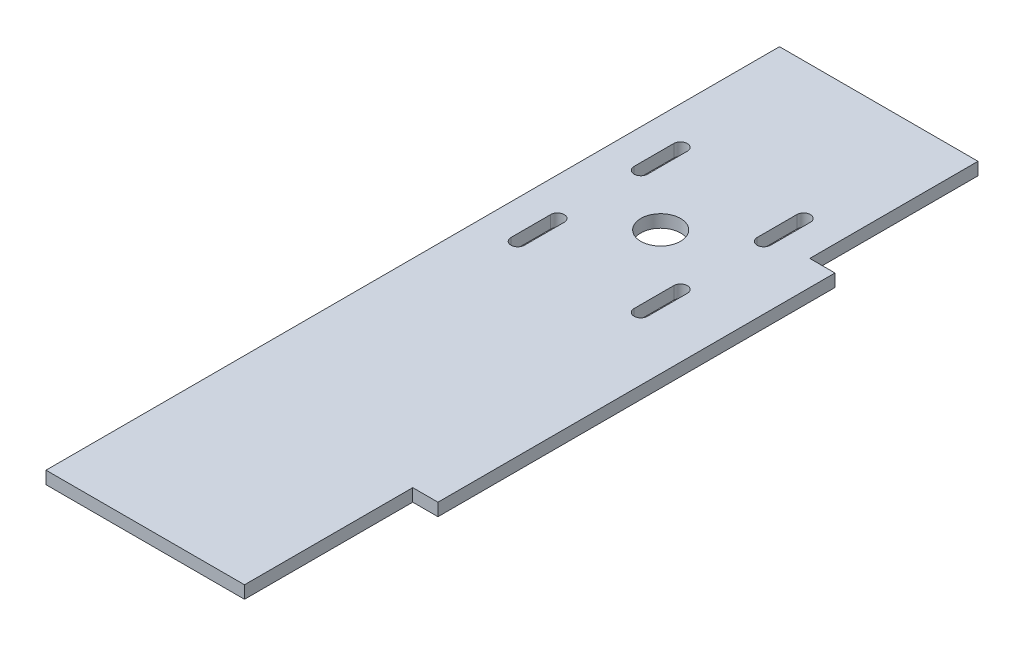
SolidWorks part; units mm, degrees
ref_plane "Front Plane" through (0, 0, 0) normal (0, 0, 1) x (1, 0, 0)
ref_plane "Top Plane" through (0, 0, 0) normal (0, 1, 0) x (1, 0, 0)
ref_plane "Right Plane" through (0, 0, 0) normal (1, 0, 0) x (0, 0, -1)
sketch "Sketch1" plane through (0, 0, 0) normal (0, 1, 0) x (1, 0, 0)
  line L0 (-25, 42.375) -> (25, 42.375)
  line L1 (25, 42.375) -> (25, 0)
  line L2 (25, 0) -> (31.35, 0)
  line L3 (31.35, 0) -> (31.35, -100)
  line L4 (31.35, -100) -> (25, -100)
  line L5 (25, -100) -> (25, -142.375)
  line L6 (25, -142.375) -> (-25, -142.375)
  line L7 (-25, -142.375) -> (-25, -100)
  line L8 (-25, -100) -> (-31.35, -100)
  line L9 (-31.35, -100) -> (-31.35, 0)
  line L10 (-31.35, 0) -> (-25, 0)
  line L11 (-25, 0) -> (-25, 42.375)
  line L12 (-25, 0) -> (-25, -100) construction
  point P11 (0, 42.375)
  point P14 (-31.35, -50)
  dimension "D1" = 6.35
  dimension "D2" = 100
  dimension "D3" = 50
  dimension "D4" = 184.75
extrude "Boss-Extrude1" add sketch "Sketch1" along normal blind 3.175 contours L11 L12 L7 L6 L5 L4 L3 L2 L1 L0 region at (1.8122, 0, 50)
sketch "Sketch2" plane through (0, 3.175, 0) normal (0, 1, 0) x (1, 0, 0)
  line L1 (25, 12.45) -> (-25, 12.45) construction
  line L2 (25, 12.45) -> (25, -37.55) construction
  line L3 (25, -37.55) -> (-25, -37.55) construction
  line L4 (-25, 12.45) -> (-25, -37.55) construction
  line L5 (0, 11.95) -> (0, -37.05) construction
  line L6 (-15.5, 2.95) -> (15.5, 2.95) construction
  line L7 (15.5, 2.95) -> (15.5, -28.05) construction
  line L8 (25, -142.375) -> (-25, -142.375) construction
  circle A0 centre (0, -12.55) radius 5
  point P5 (0, -37.55)
  point P8 (0, -142.375)
  point P9 (0, 11.95)
  point P10 (0, -37.05)
  point P13 (25, -12.55)
  point P14 (0, -12.55)
  point P15 (15.5, 2.95)
  point P16 (-15.5, 2.95)
  point P17 (15.5, -28.05)
  point P18 (-15.5, -28.05)
  point P21 (0, 2.95)
  point P22 (15.5, -12.55)
  dimension "D6" = 10
  dimension "D2" = 50
  dimension "D5" = 49
  dimension "D3" = 31
  dimension "D1" = 129.825
extrude "Cut-Extrude1" cut sketch "Sketch2" against normal through all
hole_wizard "M3 Clearance Hole1" positions "Sketch6" profile "Sketch5" hole size "M3" standard "ANSI Metric" end condition through all
sketch "Sketch6" plane through (0, 3.175, 0) normal (0, 1, 0) x (1, 0, 0)
  point P6 (-15.5, 2.95)
  point P9 (15.5, 2.95)
  point P12 (15.5, -28.05)
  point P15 (-15.5, -28.05)
sketch "Sketch5" plane through (-15.5, 3.175, -2.95) normal (1, 0, 0) x (0, 0, 1)
  line L0 (0, 0) -> (0, 3.175)
  line L1 (0, 3.175) -> (1.7, 3.175)
  line L2 (1.7, 3.175) -> (1.7, 0)
  line L5 (1.7, 0) -> (0, 0)
  line L11 (0, -6.35) -> (0, 107.95) construction
  dimension "Thru Hole Dia." = 3.4
  dimension "Thru Hole Depth" = 3.175
sketch "Sketch7" plane through (0, 3.175, 0) normal (0, 1, 0) x (1, 0, 0)
  line L0 (15.5, 7.95) -> (15.5, -2.05) construction
  line L1 (17.2, 7.95) -> (17.2, -2.05)
  line L2 (13.8, 7.95) -> (13.8, -2.05)
  line L3 (-15.5, 7.95) -> (-15.5, -2.05) construction
  line L4 (-13.8, 7.95) -> (-13.8, -2.05)
  line L5 (-17.2, 7.95) -> (-17.2, -2.05)
  line L6 (21.8073, -12.55) -> (-21.8073, -12.55) construction
  line L7 (15.5, -33.05) -> (15.5, -23.05) construction
  line L8 (17.2, -33.05) -> (17.2, -23.05)
  line L9 (13.8, -33.05) -> (13.8, -23.05)
  line L10 (-15.5, -33.05) -> (-15.5, -23.05) construction
  line L11 (-13.8, -33.05) -> (-13.8, -23.05)
  line L12 (-17.2, -33.05) -> (-17.2, -23.05)
  arc A0 (17.2, 7.95) -> (13.8, 7.95) centre (15.5, 7.95) ccw
  arc A1 (13.8, -2.05) -> (17.2, -2.05) centre (15.5, -2.05) ccw
  arc A2 (-13.8, 7.95) -> (-17.2, 7.95) centre (-15.5, 7.95) ccw
  arc A3 (-17.2, -2.05) -> (-13.8, -2.05) centre (-15.5, -2.05) ccw
  circle A4 centre (-15.5, 2.95) radius 1.7 construction
  circle A5 centre (15.5, 2.95) radius 1.7 construction
  circle A6 centre (0, -12.55) radius 5 construction
  arc A7 (17.2, -33.05) -> (13.8, -33.05) centre (15.5, -33.05) cw
  arc A8 (13.8, -23.05) -> (17.2, -23.05) centre (15.5, -23.05) cw
  arc A9 (-13.8, -33.05) -> (-17.2, -33.05) centre (-15.5, -33.05) cw
  arc A10 (-17.2, -23.05) -> (-13.8, -23.05) centre (-15.5, -23.05) cw
  point P2 (15.5, 2.95)
  point P9 (-15.5, 2.95)
  point P22 (0, -12.55)
  point P27 (15.5, -28.05)
  point P34 (-15.5, -28.05)
  dimension "D1" = 10
extrude "Cut-Extrude2" cut sketch "Sketch7" against normal through all
sketch "Sketch8" plane through (0, 3.175, 0) normal (0, 1, 0) x (1, 0, 0)
  line L8 (-25, 42.375) -> (-25, -142.375)
  line L9 (-25, -142.375) -> (25, -142.375)
  line L10 (25, -142.375) -> (25, -100)
  line L11 (25, -100) -> (31.35, -100)
  line L12 (31.35, -100) -> (31.35, 0)
  line L13 (31.35, 0) -> (25, 0)
  line L14 (25, 0) -> (25, 42.375)
  line L15 (25, 42.375) -> (-25, 42.375)
  line L16 (-25, 42.375) -> (-25, -142.375)
  line L17 (-25, -142.375) -> (25, -142.375)
  line L18 (25, -142.375) -> (25, -100)
  line L19 (25, -100) -> (31.35, -100)
  line L20 (31.35, -100) -> (31.35, 0)
  line L21 (31.35, 0) -> (25, 0)
  line L22 (25, 0) -> (25, 42.375)
  line L23 (25, 42.375) -> (-25, 42.375)
  line L32 (13.8, 7.95) -> (13.8, -2.05) construction
  line L33 (17.2, -2.05) -> (17.2, 7.95) construction
  line L34 (-13.8, -2.05) -> (-13.8, 7.95) construction
  line L35 (-17.2, 7.95) -> (-17.2, -2.05) construction
  line L36 (-17.2, -23.05) -> (-17.2, -33.05) construction
  line L37 (-13.8, -33.05) -> (-13.8, -23.05) construction
  line L38 (13.8, -23.05) -> (13.8, -33.05) construction
  line L39 (17.2, -33.05) -> (17.2, -23.05) construction
  line L40 (13.8, 7.95) -> (13.8, -2.05)
  line L41 (17.2, -2.05) -> (17.2, 7.95)
  line L42 (-13.8, -2.05) -> (-13.8, 7.95)
  line L43 (-17.2, 7.95) -> (-17.2, -2.05)
  line L44 (-17.2, -23.05) -> (-17.2, -33.05)
  line L45 (-13.8, -33.05) -> (-13.8, -23.05)
  line L46 (13.8, -23.05) -> (13.8, -33.05)
  line L47 (17.2, -33.05) -> (17.2, -23.05)
  arc A0 (17.2, 7.95) -> (13.8, 7.95) centre (15.5, 7.95) ccw construction
  arc A1 (13.8, -2.05) -> (17.2, -2.05) centre (15.5, -2.05) ccw construction
  arc A2 (-13.8, 7.95) -> (-17.2, 7.95) centre (-15.5, 7.95) ccw construction
  arc A3 (-17.2, -2.05) -> (-13.8, -2.05) centre (-15.5, -2.05) ccw construction
  arc A4 (-13.8, -23.05) -> (-17.2, -23.05) centre (-15.5, -23.05) ccw construction
  arc A5 (-17.2, -33.05) -> (-13.8, -33.05) centre (-15.5, -33.05) ccw construction
  circle A6 centre (0, -12.55) radius 5 construction
  arc A7 (17.2, -23.05) -> (13.8, -23.05) centre (15.5, -23.05) ccw construction
  arc A8 (13.8, -33.05) -> (17.2, -33.05) centre (15.5, -33.05) ccw construction
  arc A9 (17.2, 7.95) -> (13.8, 7.95) centre (15.5, 7.95) ccw
  arc A10 (13.8, -2.05) -> (17.2, -2.05) centre (15.5, -2.05) ccw
  arc A11 (-13.8, 7.95) -> (-17.2, 7.95) centre (-15.5, 7.95) ccw
  arc A12 (-17.2, -2.05) -> (-13.8, -2.05) centre (-15.5, -2.05) ccw
  arc A13 (-13.8, -23.05) -> (-17.2, -23.05) centre (-15.5, -23.05) ccw
  arc A14 (-17.2, -33.05) -> (-13.8, -33.05) centre (-15.5, -33.05) ccw
  circle A15 centre (0, -12.55) radius 5
  arc A16 (17.2, -23.05) -> (13.8, -23.05) centre (15.5, -23.05) ccw
  arc A17 (13.8, -33.05) -> (17.2, -33.05) centre (15.5, -33.05) ccw
  dimension "D1" = 0
equation "\"length\" = 184.75mm"
equation "\"w_mach\"= 60mm"
equation "\"w_tab\"= 100mm"
equation "\"t_wood\"= 0.125in"
equation "\"t_side\"= 0.25in"
equation "\"D1@Sketch1\"=\"t_side\""
equation "\"D2@Sketch1\"=\"w_tab\""
equation "\"D3@Sketch1\"=\"l_motor\""
equation "\"D4@Sketch1\"=\"length\""
equation "\"D1@Boss-Extrude1\"=\"t_wood\""
equation "\"dX\"= 144.825mm"
equation "\"in_rad\"= 15mm"
equation "\"D1@Sketch2\"=\"dX\"-\"in_rad\""
equation "\"l_motor\" = 50mm"
equation "\"l_servo\"= 40mm"
equation "\"servocenter\"= 6.35mm"
equation "\"D2@Sketch2\"=\"l_motor\""
equation "\"D3@Sketch2\"=31"
equation "\"servoholes\"= 49mm"
equation "\"D5@Sketch2\"= \"servoholes\""
